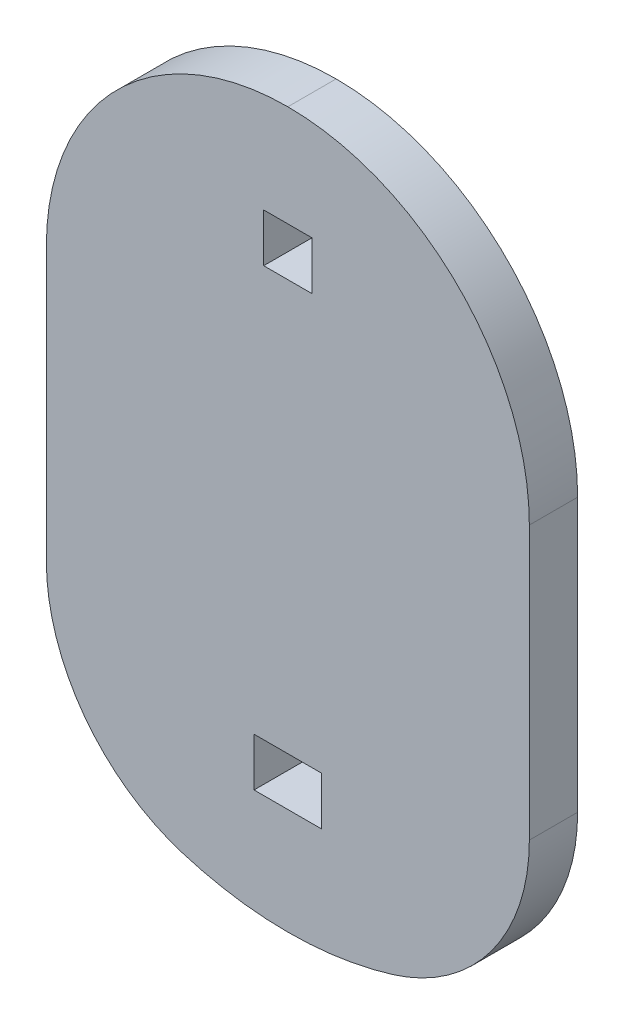
SolidWorks part; units mm, degrees
material "Acrylic (Medium-high impact)"
ref_plane "Front Plane" through (0, 0, 0) normal (0, 0, 1) x (1, 0, 0)
ref_plane "Top Plane" through (0, 0, 0) normal (0, 1, 0) x (1, 0, 0)
ref_plane "Right Plane" through (0, 0, 0) normal (1, 0, 0) x (0, 0, -1)
sketch "Sketch1" plane through (0, 0, 0) normal (0, 0, 1) x (1, 0, 0)
  circle A0 centre (0, 0) radius 37
  dimension "D1" = 74
extrude "Boss-Extrude1" add sketch "Sketch1" along normal blind 5
sketch "Sketch6" plane through (0, 0, 5) normal (0, 0, 1) x (1, 0, 0)
  line L0 (-25, 27.2764) -> (-25, -27.2764)
  line L1 (25, -27.2764) -> (25, 27.2764)
  arc A0 (25, -27.2764) -> (25, 27.2764) centre (0, 0) ccw
  circle A1 centre (0, 0) radius 37
  arc A2 (-25, 27.2764) -> (-25, -27.2764) centre (0, 0) ccw
  dimension "D2" = 25
  dimension "D3" = 50
  dimension "D1" = 0
extrude "Cut-Extrude3" cut sketch "Sketch6" against normal blind 10
fillet "Fillet2" radius 25 2 edges at (-25, 27.2764, 2.5) (25, 27.2764, 2.5)
fillet "Fillet3" radius 20 2 edges at (25, -27.2764, 2.5) (-25, -27.2764, 2.5)
sketch "Sketch7" plane through (0, 0, 5) normal (0, 0, 1) x (1, 0, 0)
  line L1 (-2.5, 26.5) -> (2.5, 26.5)
  line L2 (-2.5, 26.5) -> (-2.5, 21.5)
  line L3 (-2.5, 21.5) -> (2.5, 21.5)
  line L4 (2.5, 26.5) -> (2.5, 21.5)
  line L5 (-3.5, -21) -> (3.5, -21)
  line L6 (-3.5, -21) -> (-3.5, -26)
  line L7 (-3.5, -26) -> (3.5, -26)
  line L8 (3.5, -21) -> (3.5, -26)
  point P9 (0, 21.5)
  point P11 (0, -21)
  dimension "D1" = 10.5
  dimension "D2" = 42.5
  dimension "D3" = 5
  dimension "D4" = 7
  dimension "D5" = 5
extrude "Cut-Extrude4" cut sketch "Sketch7" against normal blind 10
sketch "Sketch2" plane through (0, 0, 5) normal (0, 0, 1) x (1, 0, 0)
  line L1 (-5, 26.5) -> (5, 26.5)
  line L2 (-5, 26.5) -> (-5, 21.5)
  line L3 (-5, 21.5) -> (5, 21.5)
  line L4 (5, 26.5) -> (5, 21.5)
  line L5 (-5, 26.5) -> (5, 21.5) construction
  line L6 (-5, 21.5) -> (5, 26.5) construction
  point P0 (0, 24)
  dimension "D1" = 5
  dimension "D2" = 26.5
  dimension "D3" = 10
extrude "Boss-Extrude2" [suppressed] add sketch "Sketch2" along normal blind 38
sketch "Sketch3" [suppressed] plane through (0, 26.5, 0) normal (0, 1, 0) x (1, 0, 0)
  line L0 (5, -5) -> (-5, -5) construction
  line L1 (5, -43) -> (-5, -43) construction
  circle A0 centre (0, -12) radius 0.5
  circle A1 centre (0, -14) radius 0.5
  circle A2 centre (0, -16) radius 0.5
  circle A3 centre (0, -18) radius 0.5
  circle A4 centre (0, -20) radius 0.5
  circle A5 centre (0, -22) radius 0.5
  circle A6 centre (0, -40.5) radius 0.5
  circle A7 centre (0, -38.5) radius 0.5
  circle A8 centre (0, -36.5) radius 0.5
  circle A9 centre (0, -34.5) radius 0.5
  circle A10 centre (0, -32.5) radius 0.5
  circle A11 centre (0, -30.5) radius 0.5
  point P20 (0, -43)
  dimension "D2" = 1
  dimension "D5" = 8.5
  dimension "D6" = 2
  dimension "D1" = 7
  dimension "D7" = 2
  dimension "D3" = 6
  dimension "D4" = 6
extrude "Cut-Extrude1" [suppressed] cut sketch "Sketch3" against normal blind 5
sketch "Sketch4" [suppressed] plane through (0, 0, 5) normal (0, 0, 1) x (1, 0, 0)
  line L1 (-7.5, -20.5) -> (7.5, -20.5)
  line L2 (-7.5, -20.5) -> (-7.5, -25.5)
  line L3 (-7.5, -25.5) -> (7.5, -25.5)
  line L4 (7.5, -20.5) -> (7.5, -25.5)
  line L5 (-7.5, -20.5) -> (7.5, -25.5) construction
  line L6 (-7.5, -25.5) -> (7.5, -20.5) construction
  line L7 (-5, 21.5) -> (5, 21.5) construction
  point P0 (0, -23)
  dimension "D1" = 42
  dimension "D2" = 15
  dimension "D3" = 5
extrude "Boss-Extrude3" [suppressed] add sketch "Sketch4" along normal blind 32
sketch "Sketch5" [suppressed] plane through (0, -20.5, 0) normal (0, 1, 0) x (1, 0, 0)
  line L0 (-7.5, -5) -> (7.5, -5) construction
  circle A0 centre (0, -26.25) radius 3.8
  dimension "D1" = 21.25
  dimension "D2" = 7.6
extrude "Cut-Extrude2" [suppressed] cut sketch "Sketch5" against normal blind 28
fillet "Fillet4" [suppressed] radius 0.5
